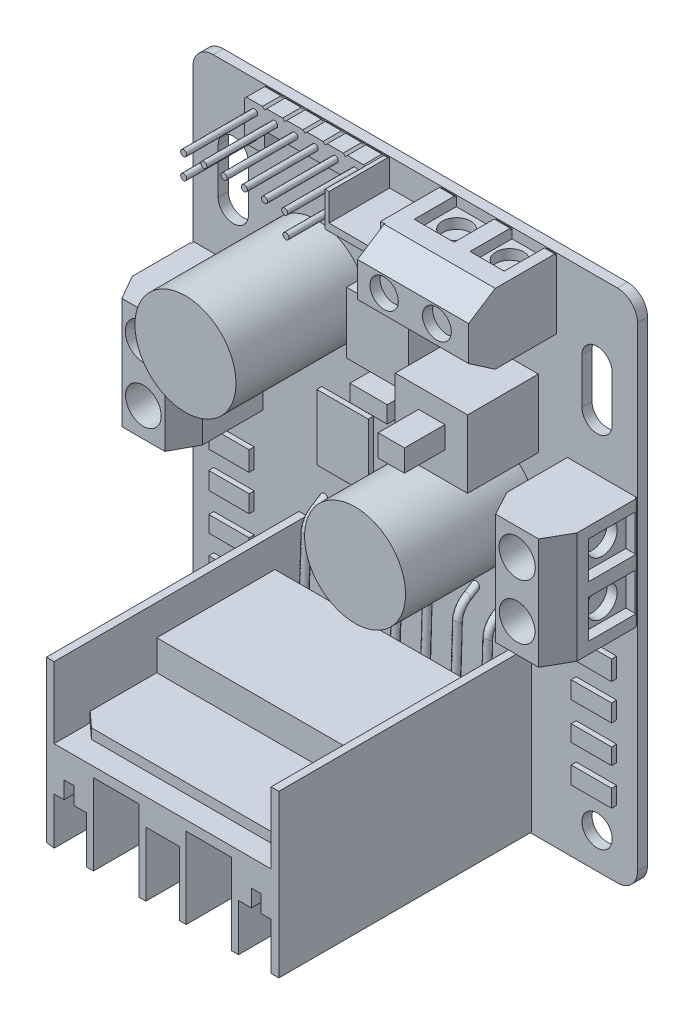
SolidWorks part; units mm, degrees
ref_plane "前视基准面" through (0, 0, 0) normal (0, 0, 1) x (1, 0, 0)
ref_plane "上视基准面" through (0, 0, 0) normal (0, 1, 0) x (1, 0, 0)
ref_plane "右视基准面" through (0, 0, 0) normal (1, 0, 0) x (0, 0, -1)
sketch "草图1" plane through (0, 0, 0) normal (0, 0, 1) x (1, 0, 0)
  line L1 (-20, 25.5) -> (20, 25.5)
  line L2 (-22, 23.5) -> (-22, -23.5)
  line L3 (-20, -25.5) -> (20, -25.5)
  line L4 (22, 23.5) -> (22, -23.5)
  line L5 (-22, 25.5) -> (22, -25.5) construction
  line L6 (-22, -25.5) -> (22, 25.5) construction
  arc A0 (20, 25.5) -> (22, 23.5) centre (20, 23.5) cw
  arc A1 (20, -25.5) -> (22, -23.5) centre (20, -23.5) ccw
  arc A2 (-22, -23.5) -> (-20, -25.5) centre (-20, -23.5) ccw
  arc A3 (-20, 25.5) -> (-22, 23.5) centre (-20, 23.5) ccw
  point P0 (0, 0)
  dimension "D3" = 2
  dimension "D1" = 51
  dimension "D2" = 44
extrude "凸台-拉伸1" add sketch "草图1" along normal blind 1
sketch "草图2" plane through (0, 0, 1) normal (0, 0, 1) x (1, 0, 0)
  line L0 (18, 18) -> (18, 13.5146) construction
  line L1 (19.5, 18) -> (19.5, 13.5146)
  line L2 (16.5, 18) -> (16.5, 13.5146)
  arc A0 (19.5, 18) -> (16.5, 18) centre (18, 18) ccw
  arc A1 (16.5, 13.5146) -> (19.5, 13.5146) centre (18, 13.5146) ccw
  point P2 (18, 15.7573)
  dimension "D3" = 1.5
  dimension "D1" = 18
  dimension "D2" = 18
extrude "切除-拉伸1" cut sketch "草图2" against normal blind 1
sketch "草图3" plane through (0, 0, 1) normal (0, 0, 1) x (1, 0, 0)
  circle A0 centre (18, -22) radius 1.5
  dimension "D3" = 3
  dimension "D1" = 18
  dimension "D2" = 22
extrude "切除-拉伸2" cut sketch "草图3" against normal blind 1
mirror "镜向2" about plane through (0, 0, 0) normal (1, 0, 0) of "切除-拉伸2", "切除-拉伸1"
sketch "草图4" plane through (0, 0, 1) normal (0, 0, 1) x (1, 0, 0)
  line L0 (-20, -25.5) -> (20, -25.5) construction
  line L1 (-11.5, -9.4) -> (11.5, -9.4)
  line L2 (-11.5, -9.4) -> (-11.5, -25.4)
  line L3 (-11.5, -25.4) -> (11.5, -25.4)
  line L4 (11.5, -9.4) -> (11.5, -25.4)
  line L5 (-11.5, -9.4) -> (11.5, -25.4) construction
  line L6 (-11.5, -25.4) -> (11.5, -9.4) construction
  point P0 (0, -17.4)
  dimension "D1" = 23
  dimension "D2" = 0
  dimension "D3" = 16
  dimension "D4" = 0.1
sketch "草图5" plane through (0, 0, 1) normal (0, 0, 1) x (1, 0, 0)
  line L0 (0, 0) -> (0, -27.3899) construction
  line L1 (-11.5, -9.4) -> (-11.5, -25.4)
  line L2 (-11.5, -25.4) -> (-10.7369, -25.4)
  line L3 (-11.5, -25.4) -> (11.5, -25.4) construction
  line L4 (-10.7369, -25.4) -> (-10.7369, -20.751)
  line L5 (-10.7369, -20.751) -> (-9.7624, -20.751)
  line L6 (-9.7624, -20.751) -> (-9.7624, -19.0456)
  line L7 (-9.7624, -19.0456) -> (-8.7878, -19.0456)
  line L8 (-8.7878, -19.0456) -> (-8.7878, -20.751)
  line L9 (-8.7878, -20.751) -> (-7.5088, -20.751)
  line L10 (-7.5088, -20.751) -> (-7.5088, -25.4)
  line L11 (-7.5088, -25.4) -> (-6.8388, -25.4)
  line L12 (-6.8388, -25.4) -> (-6.8388, -17.4)
  line L13 (-6.8388, -17.4) -> (-2.3316, -17.4)
  line L14 (-2.3316, -17.4) -> (-2.3316, -25.4)
  line L15 (-2.3316, -25.4) -> (-1.6617, -25.4)
  line L16 (-1.6617, -25.4) -> (-1.6617, -19.0456)
  line L17 (-1.6617, -19.0456) -> (1.6617, -19.0456)
  line L18 (7.5088, -25.4) -> (6.8388, -25.4)
  line L19 (2.3316, -25.4) -> (1.6617, -25.4)
  line L20 (1.6617, -25.4) -> (1.6617, -19.0456)
  line L21 (2.3316, -17.4) -> (2.3316, -25.4)
  line L22 (6.8388, -17.4) -> (2.3316, -17.4)
  line L23 (6.8388, -25.4) -> (6.8388, -17.4)
  line L24 (7.5088, -20.751) -> (7.5088, -25.4)
  line L25 (8.7878, -20.751) -> (7.5088, -20.751)
  line L26 (9.7624, -19.0456) -> (8.7878, -19.0456)
  line L27 (8.7878, -19.0456) -> (8.7878, -20.751)
  line L28 (9.7624, -20.751) -> (9.7624, -19.0456)
  line L29 (10.7369, -20.751) -> (9.7624, -20.751)
  line L30 (10.7369, -25.4) -> (10.7369, -20.751)
  line L31 (-10.7369, -25.4) -> (-11.5, -25.4)
  line L32 (-11.5, -9.4) -> (-10.7369, -9.4)
  line L33 (-11.5, -9.4) -> (11.5, -9.4) construction
  line L34 (-10.7369, -9.4) -> (-10.7369, -16.4322)
  line L35 (-10.7369, -16.4322) -> (10.7369, -16.4322)
  line L36 (11.5, -9.4) -> (10.7369, -9.4)
  line L37 (10.7369, -9.4) -> (10.7369, -16.4322)
  line L38 (11.5, -9.4) -> (11.5, -25.4)
  line L39 (-11.5, -25.2796) -> (-10.7369, -25.4)
  line L40 (10.7369, -25.4) -> (11.5, -25.4)
  point P38 (0, -19.0456)
  point P47 (0, -16.4322)
extrude "凸台-拉伸3" add sketch "草图5" along normal blind 25 contours L0 L35 L34 L32 L1 L39 L4 L5 L6 L7 L8 L9 L10 L11 L12 L13 L14 L15 L16 L17 | L35 L0 L17 L20 L19 L21 L22 L23 L18 L24 L25 L27 L26 L28 L29 L30 L40 L38 L36 L37 region at (7.2159, -18.596, 1) region at (-7.2118, -18.5891, 1)
sketch "草图6" plane through (0, -16.4322, 0) normal (0, 1, 0) x (1, 0, 0)
  line L0 (-10.7369, -26) -> (-10.7369, -1) construction
  line L1 (-10.7369, -4.1456) -> (10.7369, -4.1456)
  line L2 (-10.7369, -4.1456) -> (-10.7369, -15.8394)
  line L3 (-10.7369, -15.8394) -> (10.7369, -15.8394)
  line L4 (10.7369, -4.1456) -> (10.7369, -15.8394)
  line L5 (10.7369, -26) -> (10.7369, -1) construction
extrude "凸台-拉伸4" add sketch "草图6" along normal blind 4
sketch "草图7" plane through (0, -16.4322, 0) normal (0, 1, 0) x (1, 0, 0)
  line L0 (-10.7369, -15.8394) -> (-10.7369, -22.4296)
  line L1 (-10.7369, -26) -> (-10.7369, -15.8394) construction
  line L2 (-10.7369, -22.4296) -> (-6.8388, -26)
  line L3 (-6.8388, -26) -> (6.84, -26)
  line L4 (-10.7369, -26) -> (10.7369, -26) construction
  line L5 (6.84, -26) -> (10.7369, -22.4294)
  line L6 (10.7369, -26) -> (10.7369, -1) construction
  line L7 (10.7369, -22.4294) -> (10.7369, -15.8394)
  line L8 (-10.7369, -15.8394) -> (10.7369, -15.8394) construction
  line L9 (-10.7369, -15.8394) -> (10.7369, -15.8394) construction
  line L10 (10.7369, -15.8394) -> (-10.7369, -15.8394)
  line L11 (0, 0) -> (0, -31.646) construction
  line L12 (20, 0) -> (-20, 0) construction
  line L13 (-9.2508, -23.7907) -> (9.2512, -23.7907)
  line M4 (10.7369, -26) -> (10.7369, -15.8394)
  line M5 (10.7369, -15.8394) -> (-10.7369, -15.8394)
  line M6 (-10.7369, -15.8394) -> (-10.7369, -26)
  dimension "D1" = 6.8388
  dimension "D2" = 6.84
  dimension "D3" = 6.5902
  dimension "D4" = 6.59
extrude "凸台-拉伸5" add sketch "草图7" along normal blind 1 contours L11 L10 L2 L13 M6 | L11 L13 L5 M5 M4 region at (-5.31, -16.4322, 19.7729) region at (5.31, -16.4322, 19.7729)
sketch "草图8" plane through (0, 0, 0) normal (1, 0, 0) x (0, 0, -1)
  line L0 (-3.0347, -16.5061) -> (-2.8136, -9.1715)
  line L2 (-1.8814, -7.5402) -> (-0.9876, -6.9764)
  arc A0 (-2.8136, -9.1715) -> (-1.8814, -7.5402) centre (-0.8145, -9.2318) cw
  dimension "D1" = 2
sketch "草图10" plane through (0, 0, 1) normal (0, 0, 1) x (1, 0, 0)
  line L0 (0, -7.5402) -> (0, -6.9764) construction
  circle A0 centre (0, -6.9764) radius 0.3747
sweep "扫描1" add profiles "草图10" path "草图8"
pattern_linear "阵列(线性)1" count 4 spacing 3 along (-1, 0, 0) of "扫描1"
pattern_linear "阵列(线性)2" count 4 spacing 3 along (1, 0, 0) of "阵列(线性)1"
sketch "草图11" plane through (0, 0, 1) normal (0, 0, 1) x (1, 0, 0)
  circle A0 centre (-9.7388, 11.4615) radius 5
  circle A1 centre (7.0481, 1.7656) radius 5
extrude "凸台-拉伸6" add sketch "草图11" along normal blind 13
sketch "草图12" plane through (0, 0, 1) normal (0, 0, 1) x (1, 0, 0)
  line L1 (5.0221, 14.2111) -> (12.1854, 14.2111)
  line L2 (5.0221, 14.2111) -> (5.0221, 7.4819)
  line L3 (5.0221, 7.4819) -> (12.1854, 7.4819)
  line L4 (12.1854, 14.2111) -> (12.1854, 7.4819)
extrude "凸台-拉伸7" add sketch "草图12" along normal blind 7
sketch "草图13" plane through (0, 0, 8) normal (0, 0, 1) x (1, 0, 0)
  line L1 (7.3375, 12.2574) -> (9.9423, 12.2574)
  line L2 (7.3375, 12.2574) -> (7.3375, 10.0867)
  line L3 (7.3375, 10.0867) -> (9.9423, 10.0867)
  line L4 (9.9423, 12.2574) -> (9.9423, 10.0867)
  line L5 (7.3375, 12.2574) -> (9.9423, 10.0867) construction
  line L6 (7.3375, 10.0867) -> (9.9423, 12.2574) construction
  point P0 (8.6399, 11.1721)
extrude "凸台-拉伸8" add sketch "草图13" along normal blind 4
sketch "草图14" plane through (0, 0, 1) normal (0, 0, 1) x (1, 0, 0)
  line L1 (-2.7925, 16.1647) -> (3.3578, 16.1647)
  line L2 (-2.7925, 16.1647) -> (-2.7925, 10.0867)
  line L3 (-2.7925, 10.0867) -> (3.3578, 10.0867)
  line L4 (3.3578, 16.1647) -> (3.3578, 10.0867)
extrude "凸台-拉伸9" add sketch "草图14" along normal blind 4
sketch "草图16" plane through (0, 0, 1) normal (0, 0, 1) x (1, 0, 0)
  line L1 (-4.4567, 6.1071) -> (-0.7665, 6.1071)
  line L2 (-4.4567, 6.1071) -> (-4.4567, 4.4429)
  line L3 (-4.4567, 4.4429) -> (-0.7665, 4.4429)
  line L4 (-0.7665, 6.1071) -> (-0.7665, 4.4429)
extrude "凸台-拉伸10" add sketch "草图16" along normal blind 2
sketch "草图17" plane through (0, 0, 1) normal (0, 0, 1) x (1, 0, 0)
  line L0 (22, -23.5) -> (22, 23.5) construction
  line L1 (22, 8.5) -> (15.0652, 8.5)
  line L2 (22, 8.5) -> (22, -2.5)
  line L3 (22, -2.5) -> (15.0652, -2.5)
  line L4 (15.0652, 8.5) -> (15.0652, -2.5)
  line L5 (20, 25.5) -> (-20, 25.5) construction
  dimension "D1" = 17
  dimension "D2" = 11
extrude "凸台-拉伸11" add sketch "草图17" along normal blind 6
sketch "草图18" plane through (0, 8.5, 0) normal (0, 1, 0) x (1, 0, 0)
  line L0 (15.0652, -1) -> (15.0652, -7)
  line L1 (15.0652, -7) -> (16.3722, -9.4071)
  line L2 (16.3722, -9.4071) -> (20.6242, -9.4071)
  line L3 (20.6242, -9.4071) -> (22, -7)
  line L4 (22, -7) -> (22, -1) construction
  line L5 (22, -7) -> (15.0652, -7) construction
  line L6 (22, -7) -> (22, -1)
  line L7 (22, -1) -> (15.0652, -1)
extrude "凸台-拉伸12" add sketch "草图18" against normal up to surface (11 mm away) up to face at (18.5326, -2.5, 4)
mirror "镜向3" about plane through (0, 0, 0) normal (1, 0, 0) of "凸台-拉伸12"
sketch "草图19" plane through (0, 0, 9.4071) normal (0, 0, 1) x (1, 0, 0)
  circle A0 centre (18.4982, 5.8549) radius 1.794
  circle A1 centre (18.4982, 0.3549) radius 1.7659
  dimension "D1" = 5.5
extrude "切除-拉伸3" cut sketch "草图19" against normal blind 3
mirror "镜向4" about plane through (0, 0, 0) normal (1, 0, 0) of "切除-拉伸3"
sketch "草图20" plane through (22, 0, 0) normal (1, 0, 0) x (0, 0, -1)
  line L1 (-5.8619, 7.4186) -> (-1.1527, 7.4186)
  line L2 (-5.8619, 7.4186) -> (-5.8619, 3.7396)
  line L3 (-5.8619, 3.7396) -> (-1.1527, 3.7396)
  line L4 (-1.1527, 7.4186) -> (-1.1527, 3.7396)
  line L5 (-5.8619, 2.4151) -> (-1.1527, 2.4151)
  line L6 (-5.8619, 2.4151) -> (-5.8619, -1.362)
  line L7 (-5.8619, -1.362) -> (-1.1527, -1.362)
  line L8 (-1.1527, 2.4151) -> (-1.1527, -1.362)
extrude "切除-拉伸4" cut sketch "草图20" against normal blind 1
mirror "镜向5" about plane through (0, 0, 0) normal (1, 0, 0) of "切除-拉伸4"
sketch "草图21" plane through (21, 0, 0) normal (1, 0, 0) x (0, 0, -1)
  circle A0 centre (-3.5073, 5.7508) radius 1.5
  circle A1 centre (-3.5073, 0.4039) radius 1.5
  dimension "D1" = 3
  dimension "D2" = 3
extrude "切除-拉伸5" cut sketch "草图21" against normal blind 1
mirror "镜向6" about plane through (0, 0, 0) normal (1, 0, 0) of "切除-拉伸5"
sketch "草图22" plane through (0, 0, 1) normal (0, 0, 1) x (1, 0, 0)
  line L0 (20, 25.5) -> (-20, 25.5) construction
  line L1 (3, 25.5) -> (14, 25.5)
  line L2 (3, 25.5) -> (3, 18.57)
  line L3 (3, 18.57) -> (14, 18.57)
  line L4 (14, 25.5) -> (14, 18.57)
  line L5 (22, 8.5) -> (22, 5.6631)
  line L6 (22, -2.5) -> (22, 8.5) construction
  line L7 (22, 8.5) -> (22, 23.5) construction
  dimension "D1" = 6.93
  dimension "D2" = 11
  dimension "D3" = 8
extrude "凸台-拉伸13" add sketch "草图22" along normal blind 5 contours L4 L1 L2 L3 region at (8.5, 22.035, 1)
sketch "草图23" plane through (14, 0, 0) normal (1, 0, 0) x (0, 0, -1)
  line L0 (-1, 25.5) -> (-7.0774, 25.5)
  line L1 (-7.0774, 25.5) -> (-9.7103, 23.7987)
  line L2 (-9.7103, 23.7987) -> (-9.7103, 20.3645)
  line L3 (-9.7103, 20.3645) -> (-7.0774, 18.57)
  line L4 (-7.0774, 18.57) -> (-1, 18.57)
  line L5 (-1, 18.57) -> (-1, 25.5)
extrude "凸台-拉伸14" add sketch "草图23" against normal up to surface (11 mm away) up to face at (3, 22.035, 3.5)
sketch "草图24" plane through (0, 0, 9.7103) normal (0, 0, 1) x (1, 0, 0)
  circle A0 centre (5.6357, 22.2217) radius 1.4023
  circle A1 centre (10.8594, 22.2217) radius 1.424
extrude "切除-拉伸6" cut sketch "草图24" against normal blind 1
sketch "草图25" plane through (0, 25.5, 0) normal (0, 1, 0) x (1, 0, 0)
  line L0 (-11.5, -1) -> (11.5, -1) construction
  line L1 (4.0685, -1) -> (8.0106, -1)
  line L2 (4.0685, -1) -> (4.0685, -5.1644)
  line L3 (4.0685, -5.1644) -> (8.0106, -5.1644)
  line L4 (8.0106, -1) -> (8.0106, -5.1644)
  line L6 (9.5874, -1) -> (12.9729, -1)
  line L7 (9.5874, -1) -> (9.5874, -5.1644)
  line L8 (9.5874, -5.1644) -> (12.9729, -5.1644)
  line L9 (12.9729, -1) -> (12.9729, -5.1644)
extrude "切除-拉伸7" cut sketch "草图25" against normal blind 1
sketch "草图26" plane through (0, 0, 1) normal (0, 0, 1) x (1, 0, 0)
  line L0 (3, 25.5) -> (-20, 25.5) construction
  line L1 (-2.9125, 25.5) -> (3, 25.5)
  line L2 (-2.9125, 25.5) -> (-2.9125, 22.0816)
  line L3 (-2.9125, 22.0816) -> (3, 22.0816)
  line L4 (3, 25.5) -> (3, 22.0816)
  line L5 (3, 20.3645) -> (3, 23.7987) construction
  line L7 (-2.5257, 25.5) -> (2.586, 25.5)
  line L8 (-2.5257, 25.5) -> (-2.5257, 22.7939)
  line L9 (-2.5257, 22.7939) -> (2.586, 22.7939)
  line L10 (2.586, 25.5) -> (2.586, 22.7939)
extrude "凸台-拉伸15" add sketch "草图26" along normal blind 6 contours L1 L10 L9 L8 L2 L3 L4 region at (-2.7191, 25.4317, 1)
sketch "草图27" plane through (0, 0, 1) normal (0, 0, 1) x (1, 0, 0)
  line L0 (-9.1172, 25.5) -> (-8.9125, 25.2953)
  line L1 (-3.1172, 25.5) -> (-4.7078, 25.5)
  line L2 (-2.9125, 25.2953) -> (-2.9125, 23.7047)
  line L3 (-3.1172, 23.5) -> (-4.7078, 23.5)
  line L4 (-4.9125, 25.2953) -> (-4.9125, 23.7047)
  line L5 (-8.9125, 23.7047) -> (-9.1172, 23.5)
  line L6 (-4.9125, 25.2953) -> (-4.7078, 25.5)
  line L7 (-3.1172, 25.5) -> (-2.9125, 25.2953)
  line L8 (-2.9125, 23.7047) -> (-3.1172, 23.5)
  line L9 (-4.7078, 23.5) -> (-4.9125, 23.7047)
  line L10 (-5.1172, 25.5) -> (-6.7078, 25.5)
  line L11 (-6.9125, 25.2953) -> (-6.9125, 23.7047)
  line L12 (-4.9125, 23.7047) -> (-5.1172, 23.5)
  line L13 (-5.1172, 25.5) -> (-4.9125, 25.2953)
  line L14 (-5.1172, 23.5) -> (-6.7078, 23.5)
  line L15 (-6.9125, 25.2953) -> (-6.7078, 25.5)
  line L16 (-4.9125, 25.2953) -> (-4.9125, 23.7047)
  line L17 (-6.7078, 23.5) -> (-6.9125, 23.7047)
  line L18 (-7.1172, 25.5) -> (-6.9125, 25.2953)
  line L19 (-7.1172, 23.5) -> (-8.7078, 23.5)
  line L20 (-8.7078, 23.5) -> (-8.9125, 23.7047)
  line L21 (-7.1172, 25.5) -> (-8.7078, 25.5)
  line L22 (-6.9125, 23.7047) -> (-7.1172, 23.5)
  line L23 (-8.9125, 25.2953) -> (-8.9125, 23.7047)
  line L24 (-8.9125, 25.2953) -> (-8.9125, 23.7047)
  line L25 (-9.1172, 25.5) -> (-10.7078, 25.5)
  line L26 (-9.1172, 23.5) -> (-10.7078, 23.5)
  line L27 (-10.9125, 25.2953) -> (-10.9125, 23.7047)
  line L28 (-10.7078, 23.5) -> (-10.9125, 23.7047)
  line L29 (-8.9125, 25.2953) -> (-8.7078, 25.5)
  line L30 (-10.9125, 25.2953) -> (-10.7078, 25.5)
  line L31 (-6.9125, 25.2953) -> (-6.9125, 23.7047)
  line L32 (-10.9125, 25.2953) -> (-10.9125, 23.7047)
  line L33 (-14.9125, 25.2953) -> (-14.7078, 25.5)
  line L34 (-11.1172, 25.5) -> (-10.9125, 25.2953)
  line L35 (-12.9125, 25.2953) -> (-12.7078, 25.5)
  line L36 (-12.9125, 23.7047) -> (-13.1172, 23.5)
  line L37 (-10.9125, 23.7047) -> (-11.1172, 23.5)
  line L38 (-10.9125, 25.2953) -> (-10.9125, 23.7047)
  line L39 (-14.7078, 23.5) -> (-14.9125, 23.7047)
  line L40 (-13.1172, 25.5) -> (-14.7078, 25.5)
  line L41 (-12.7078, 23.5) -> (-12.9125, 23.7047)
  line L42 (-11.1172, 23.5) -> (-12.7078, 23.5)
  line L43 (-13.1172, 23.5) -> (-14.7078, 23.5)
  line L44 (-12.9125, 25.2953) -> (-12.9125, 23.7047)
  line L45 (-11.1172, 25.5) -> (-12.7078, 25.5)
  line L46 (-13.1172, 25.5) -> (-12.9125, 25.2953)
  line L47 (-14.9125, 25.2953) -> (-14.9125, 23.7047)
  line L48 (-12.9125, 25.2953) -> (-12.9125, 23.7047)
  line L49 (-13.1172, 23.5) -> (-14.7078, 23.5)
  line L50 (-12.9125, 21.7047) -> (-13.1172, 21.5)
  line L51 (-14.7078, 21.5) -> (-14.9125, 21.7047)
  line L52 (-13.1172, 23.5) -> (-12.9125, 23.2953)
  line L53 (-12.9125, 23.2953) -> (-12.9125, 21.7047)
  line L54 (-14.9125, 23.2953) -> (-14.9125, 21.7047)
  line L55 (-14.9125, 23.2953) -> (-14.7078, 23.5)
  line L56 (-12.9125, 23.2953) -> (-12.9125, 21.7047)
  line L57 (-13.1172, 21.5) -> (-14.7078, 21.5)
  line L58 (-4.9125, 23.2953) -> (-4.7078, 23.5)
  line L59 (-2.9125, 23.2953) -> (-2.9125, 21.7047)
  line L60 (-4.7078, 21.5) -> (-4.9125, 21.7047)
  line L61 (-3.1172, 21.5) -> (-4.7078, 21.5)
  line L62 (-2.9125, 21.7047) -> (-3.1172, 21.5)
  line L63 (-3.1172, 23.5) -> (-4.7078, 23.5)
  line L64 (-4.9125, 23.2953) -> (-4.9125, 21.7047)
  line L65 (-3.1172, 23.5) -> (-4.7078, 23.5)
  line L66 (-2.9125, 23.2953) -> (-2.9125, 21.7047)
  line L67 (-3.1172, 23.5) -> (-2.9125, 23.2953)
  point P21 (-3.9125, 24.5)
  point P33 (-7.9125, 24.5)
  point P52 (-11.9125, 24.5)
  dimension "D3" = 4
extrude "凸台-拉伸16" add sketch "草图27" along normal blind 2 contours L33 L47 L39 L43 L36 L44 L46 L40 | L57 L50 L53 L52 L43 L55 L54 L51 | L34 L45 L35 L44 L41 L42 L37 L27 | L30 L27 L28 L26 L5 L23 L0 L25 | L29 L23 L20 L19 L22 L11 L18 L21 | L17 L14 L12 L4 L13 L10 L15 L11 | L9 L3 L8 L2 L7 L1 L6 L4 | L67 L3 L58 L64 L60 L61 L62 L59 region at (-9.9125, 24.5, 1) region at (-7.9125, 24.5, 1) region at (-11.9125, 24.5, 1) region at (-5.9125, 24.5, 1) region at (-13.9125, 24.5, 1) region at (-3.9125, 24.5, 1) region at (-13.9125, 22.5, 1) region at (-3.9125, 22.5, 1)
sketch "草图28" plane through (0, 0, 3) normal (0, 0, 1) x (1, 0, 0)
  circle A0 centre (-13.9125, 24.5906) radius 0.3
  circle A1 centre (-11.9125, 24.5906) radius 0.3
  circle A2 centre (-9.9125, 24.5906) radius 0.3
  circle A3 centre (-7.9125, 24.5906) radius 0.3
  circle A4 centre (-5.9125, 24.5906) radius 0.3
  circle A5 centre (-3.9125, 24.5906) radius 0.3
  circle A6 centre (-13.9125, 22.5408) radius 0.3
  circle A7 centre (-3.7888, 22.5408) radius 0.3
  dimension "D1" = 0.6
  dimension "D3" = 0.6
  dimension "D4" = 0.6
  dimension "D2" = 6
extrude "凸台-拉伸17" add sketch "草图28" along normal blind 7
sketch "草图29" plane through (0, 0, 1) normal (0, 0, 1) x (1, 0, 0)
  line L0 (0, 0) -> (0, -34.3092) construction
  line L1 (-9.2384, 2.4293) -> (-4.1455, 2.4293)
  line L2 (-9.2384, 2.4293) -> (-9.2384, -4.0401)
  line L3 (-9.2384, -4.0401) -> (-4.1455, -4.0401)
  line L4 (-4.1455, 2.4293) -> (-4.1455, -4.0401)
  line L5 (15.9333, -6.0904) -> (19.9319, -6.0904)
  line L6 (15.9333, -6.0904) -> (15.9333, -8.0325)
  line L7 (15.9333, -8.0325) -> (19.9319, -8.0325)
  line L8 (19.9319, -6.0904) -> (19.9319, -8.0325)
  line L9 (15.9333, -9.8605) -> (19.9319, -9.8605)
  line L10 (15.9333, -9.8605) -> (15.9333, -11.5742)
  line L11 (15.9333, -11.5742) -> (19.9319, -11.5742)
  line L12 (19.9319, -9.8605) -> (19.9319, -11.5742)
  line L13 (15.9333, -13.6306) -> (19.9319, -13.6306)
  line L14 (15.9333, -13.6306) -> (15.9333, -15.23)
  line L15 (15.9333, -15.23) -> (19.9319, -15.23)
  line L16 (19.9319, -13.6306) -> (19.9319, -15.23)
  line L17 (15.9333, -17.1722) -> (19.9319, -17.1722)
  line L18 (15.9333, -17.1722) -> (15.9333, -18.8859)
  line L19 (15.9333, -18.8859) -> (19.9319, -18.8859)
  line L20 (19.9319, -17.1722) -> (19.9319, -18.8859)
  line L21 (-19.9319, -17.1722) -> (-19.9319, -18.8859)
  line L22 (-15.9333, -18.8859) -> (-19.9319, -18.8859)
  line L23 (-15.9333, -17.1722) -> (-15.9333, -18.8859)
  line L24 (-15.9333, -17.1722) -> (-19.9319, -17.1722)
  line L25 (-19.9319, -13.6306) -> (-19.9319, -15.23)
  line L26 (-15.9333, -15.23) -> (-19.9319, -15.23)
  line L27 (-15.9333, -13.6306) -> (-15.9333, -15.23)
  line L28 (-15.9333, -13.6306) -> (-19.9319, -13.6306)
  line L29 (-19.9319, -9.8605) -> (-19.9319, -11.5742)
  line L30 (-15.9333, -11.5742) -> (-19.9319, -11.5742)
  line L31 (-15.9333, -9.8605) -> (-15.9333, -11.5742)
  line L32 (-15.9333, -9.8605) -> (-19.9319, -9.8605)
  line L33 (-19.9319, -6.0904) -> (-19.9319, -8.0325)
  line L34 (-15.9333, -8.0325) -> (-19.9319, -8.0325)
  line L35 (-15.9333, -6.0904) -> (-15.9333, -8.0325)
  line L36 (-15.9333, -6.0904) -> (-19.9319, -6.0904)
extrude "凸台-拉伸18" add sketch "草图29" along normal blind 0.5
sketch "草图30" plane through (0, 25.5, 0) normal (0, 1, 0) x (1, 0, 0)
  line L0 (14, -7.0774) -> (14, -1) construction
  line L1 (-14.9125, -1) -> (14, -1)
  line L2 (-14.9125, -1) -> (-14.9125, -1.1809)
  line L3 (-14.9125, -1.1809) -> (14, -1.1809)
  line L4 (14, -1) -> (14, -1.1809)
extrude "切除-拉伸8" cut sketch "草图30" against normal blind 0.1
ref_plane "基准面1" through (22, 7.4186, 5.8619) normal (0, -1, 0) x (-1, 0, 0)
sketch "草图32" plane through (22, 0, 0) normal (1, 0, 0) x (0, 0, -1)
  line L0 (-7, -2.5) -> (-1, -2.5) construction
  line L1 (-1, 8.5) -> (-1.1541, 8.5)
  line L2 (-1, 8.5) -> (-1, -2.5)
  line L3 (-1, -2.5) -> (-1.1541, -2.5)
  line L4 (-1.1541, 8.5) -> (-1.1541, -2.5)
extrude "切除-拉伸9" cut sketch "草图32" against normal blind 0.1
sketch "草图33" plane through (-22, 0, 0) normal (-1, 0, 0) x (0, 0, 1)
  line L0 (1, -2.5) -> (7, -2.5) construction
  line L1 (1, 8.5) -> (1.2523, 8.5)
  line L2 (1, 8.5) -> (1, -2.5)
  line L3 (1, -2.5) -> (1.2523, -2.5)
  line L4 (1.2523, 8.5) -> (1.2523, -2.5)
extrude "切除-拉伸10" cut sketch "草图33" against normal blind 0.1
sketch "草图34" plane through (0, 24.5, 0) normal (0, 1, 0) x (1, 0, 0)
  circle A0 centre (6.0131, -2.9173) radius 1.395
  circle A1 centre (11.2802, -2.9173) radius 1.3751
extrude "切除-拉伸12" cut sketch "草图34" against normal blind 1
